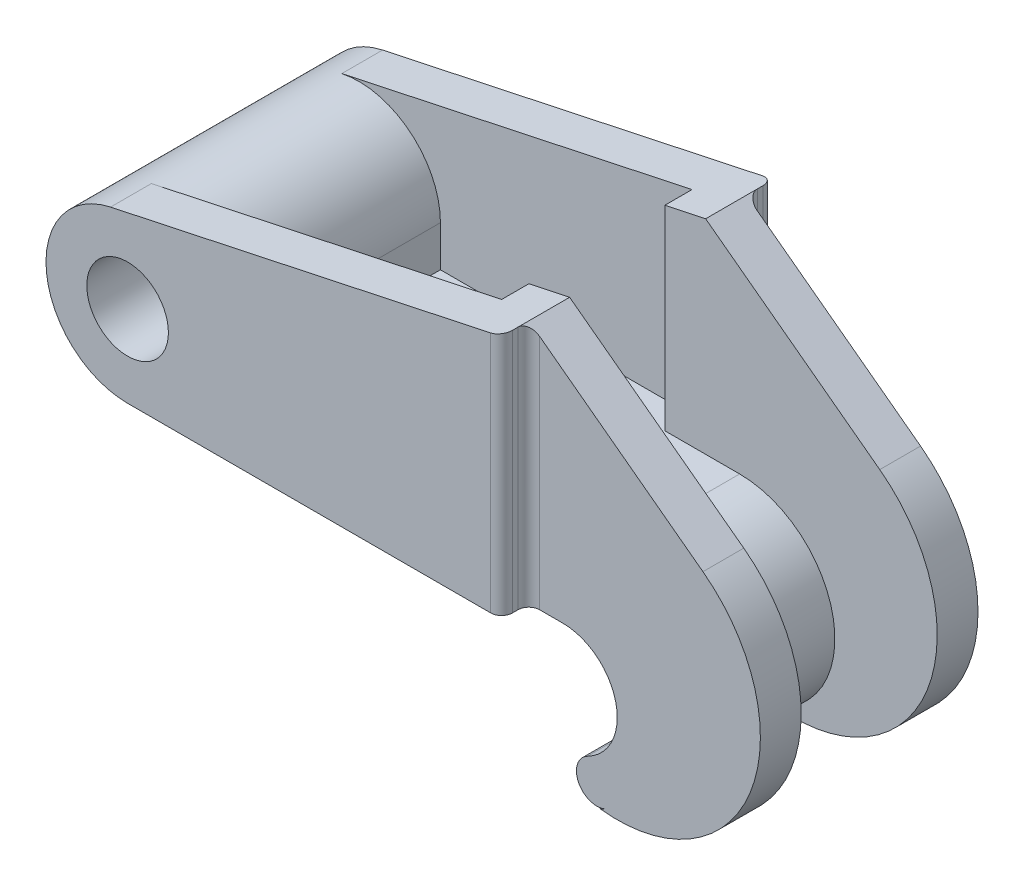
SolidWorks part; units mm, degrees
ref_plane "Front Plane" through (0, 0, 0) normal (0, 0, 1) x (1, 0, 0)
ref_plane "Top Plane" through (0, 0, 0) normal (0, 1, 0) x (1, 0, 0)
ref_plane "Right Plane" through (0, 0, 0) normal (1, 0, 0) x (0, 0, -1)
sketch "Sketch1" plane through (0, 0, 0) normal (0, 0, 1) x (1, 0, 0)
  line L0 (0, -19.05) -> (87.3125, -19.05)
  line L1 (87.3125, 38.1) -> (87.3125, -19.05)
  line L2 (87.3125, 38.1) -> (-3.9735, 18.631)
  line L4 (19.05, 0) -> (19.05, -19.05)
  line L5 (87.3125, -19.05) -> (141.3653, -19.05)
  line L6 (87.3125, 38.1) -> (127.9582, 7.713)
  line L7 (95.25, -9.525) -> (19.05, -9.525)
  line L8 (77.7875, -19.05) -> (77.7875, 36.0686)
  circle A0 centre (0, 0) radius 9.525
  arc A1 (19.05, 0) -> (0, -19.05) centre (0, 0) ccw
  arc A2 (101.0227, -43.0622) -> (95.25, -19.05) centre (95.25, -31.75) ccw
  arc A3 (101.0227, -43.0622) -> (105.3523, -51.5463) centre (103.1875, -47.3043) ccw
  arc A4 (102.3959, -52.0005) -> (127.9582, 7.713) centre (107.95, -19.05) ccw
  arc A5 (103.9067, -52.2198) -> (95.25, -9.525) centre (95.25, -31.75) ccw
  dimension "D1" = 19.05
  dimension "D2" = 38.1
  dimension "D7" = 9.525
  dimension "D6" = 25.4
  dimension "D3" = 87.3125
  dimension "D4" = 57.15
  dimension "D5" = 93.3391
  dimension "D8" = 7.9375
  dimension "D9" = 12.7
  dimension "D10" = 12.7
  dimension "D11" = 95.25
  dimension "D12" = 77.7875
  dimension "D13" = 19.05
  dimension "D14" = 76.2
  dimension "D15" = 36.0686
extrude "Boss-Extrude1" add sketch "Sketch1" along normal mid plane 31.75 contours L0 L8 L7 L4 | L5 A5 L7 L8 L0 | A3 A5 L5 A2 | L4 A1 L0 A0 | L8 L0 L1 L7 region at (-18.4091, -1.9413, 0) region at (48.4188, -14.2875, 0) region at (82.55, -14.2875, 0) region at (98.106, -14.826, 0) region at (109.1758, -35.2616, 0)
extrude "Boss-Extrude2" add sketch "Sketch1<3>" along normal mid plane 44.45 contours L0 L8 L7 L4 | L4 A1 L0 A0 region at (-18.4091, -1.9413, 0) region at (48.4188, -14.2875, 0)
sketch "Sketch1<3>" plane through (0, 0, 0) normal (0, 0, 1) x (1, 0, 0) same geometry as "Sketch1"
extrude "Boss-Extrude6" add sketch "Sketch1<7>" along normal blind 9.525 from offset 22.225 contours L4 A1 L0 A0 | L0 L8 L7 L4 | A1 L4 L7 L8 L2 | L8 L7 L1 L2 | L8 L0 L1 L7 region at (-18.4091, -1.9413, 0) region at (48.4188, -14.2875, 0) region at (48.1129, 10.6491, 0) region at (82.55, -14.2875, 0) region at (82.5846, 13.7833, 0)
sketch "Sketch1<7>" plane through (0, 0, 0) normal (0, 0, 1) x (1, 0, 0) same geometry as "Sketch1"
extrude "Boss-Extrude8" add sketch "Sketch1<9>" along normal blind 9.525 from offset 15.875 contours L8 L7 L1 L2 | L8 L0 L1 L7 region at (82.55, -14.2875, 0) region at (82.5846, 13.7833, 0)
sketch "Sketch1<9>" plane through (0, 0, 0) normal (0, 0, 1) x (1, 0, 0) same geometry as "Sketch1"
extrude "Boss-Extrude10" add sketch "Sketch1<10>" along normal blind 9.525 from offset 15.875 contours A5 A4 L6 L1 L7 | A3 A5 L5 A2 | L5 A5 L7 L1 | A5 A4 L5 region at (98.106, -14.826, 0) region at (110.005, 3.1865, 0) region at (109.1758, -35.2616, 0) region at (125.5284, -33.4955, 0)
sketch "Sketch1<10>" plane through (0, 0, 0) normal (0, 0, 1) x (1, 0, 0) same geometry as "Sketch1"
mirror "Mirror1" about plane through (0, 0, 0) normal (0, 0, 1) of "Boss-Extrude8", "Boss-Extrude6", "Boss-Extrude10"
sketch "Sketch2" plane through (0, -9.525, 0) normal (0, 1, 0) x (1, 0, 0)
  line L0 (28.575, -15.875) -> (28.575, 15.875)
  line L1 (95.25, 0) -> (19.05, 0) construction
  line L2 (28.575, 15.875) -> (43.2693, 15.875)
  line L3 (46.5563, 15.4423) -> (81.2966, 6.1336)
  line L4 (19.05, -22.225) -> (19.05, 22.225) construction
  line L5 (77.7875, 22.225) -> (19.05, 22.225) construction
  line L6 (19.05, 0) -> (95.25, 0) construction
  line L7 (-19.05, 0) -> (19.05, 0) construction
  line L8 (95.25, -15.875) -> (95.25, 15.875) construction
  line L9 (46.5563, -15.4423) -> (81.2966, -6.1336)
  line L10 (28.575, -15.875) -> (43.2693, -15.875)
  arc A0 (43.2693, 15.875) -> (46.5563, 15.4423) centre (43.2693, 3.175) cw
  circle A1 centre (79.6531, 0) radius 6.35
  arc A2 (43.2693, -15.875) -> (46.5563, -15.4423) centre (43.2693, -3.175) ccw
  point P25 (28.575, 0)
  dimension "D3" = 12.7
  dimension "D4" = 12.7
  dimension "D1" = 9.525
  dimension "D2" = 6.35
  dimension "D5" = 15
  dimension "D6" = 51.0781
extrude "Cut-Extrude1" cut sketch "Sketch2" against normal through all contours L0 L6 A1 L3 A0 L2 | L6 L0 L10 A2 L9 A1 | A1 L6 | L6 A1 region at (49.3, -9.525, 6.9404) region at (49.3, -9.525, -6.9404) region at (79.6531, -9.525, -2.695) region at (79.6531, -9.525, 2.695)
fillet "Fillet1" radius 2.54 4 edges at (87.3125, 9.525, -31.75) (87.3125, 9.525, -25.4) (87.3125, 9.525, 31.75) (87.3125, 9.525, 25.4)
